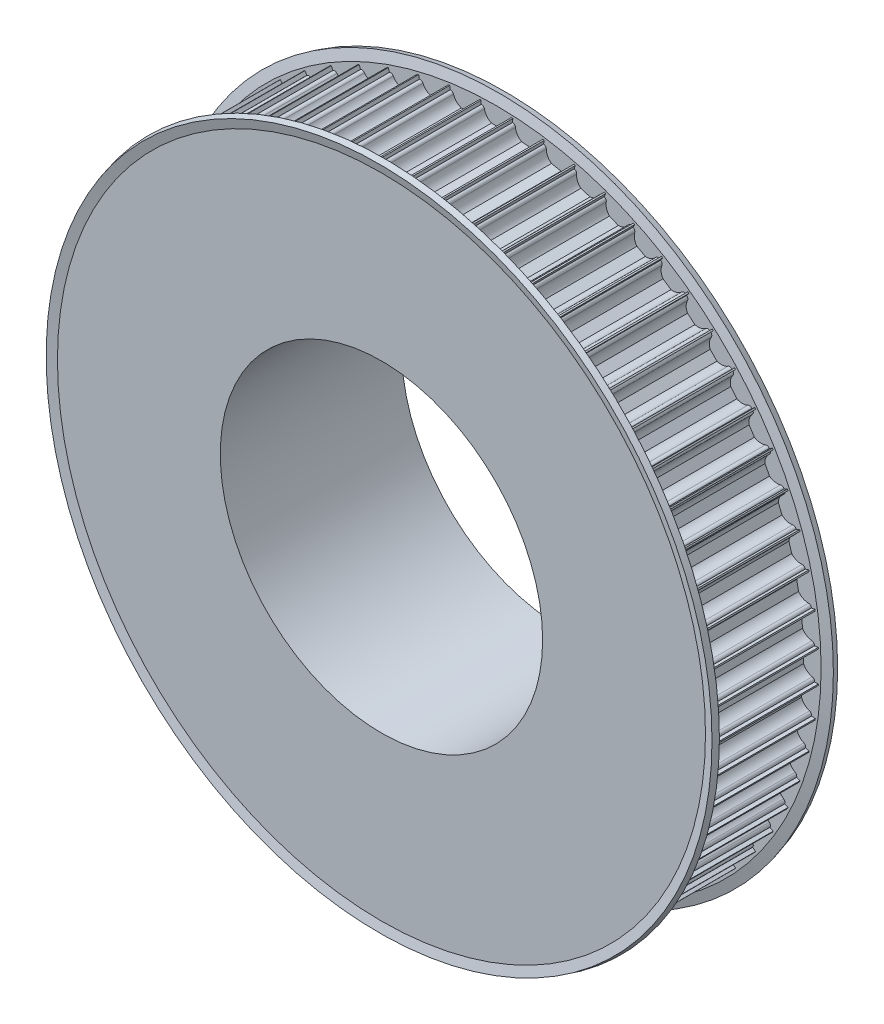
SolidWorks part; units mm, degrees
ref_plane "Front Plane" through (0, 0, 0) normal (0, 0, 1) x (1, 0, 0)
ref_plane "Top Plane" through (0, 0, 0) normal (0, 1, 0) x (1, 0, 0)
ref_plane "Right Plane" through (0, 0, 0) normal (1, 0, 0) x (0, 0, -1)
sketch "Sketch1" plane through (0, 0, 0) normal (1, 0, 0) x (0, 0, -1)
  line L0 (0, 0) -> (39.9222, 0) construction
  line L1 (0, 40) -> (45, 40)
  line L2 (45, 40) -> (45, 55.5)
  line L3 (45, 55.5) -> (30, 55.5)
  line L4 (30, 55.5) -> (30, 80)
  line L5 (30, 80) -> (0, 80)
  line L6 (0, 80) -> (0, 40)
  dimension "D1" = 80
  dimension "D2" = 40
  dimension "D3" = 15.5
  dimension "D4" = 15
  dimension "D5" = 30
revolve "Revolve1" add sketch "Sketch1" angle 360 about L0
sketch "Sketch2" plane through (0, 0, 0) normal (0, 0, 1) x (1, 0, 0)
  line L0 (-3.6742, 79) -> (-3.75, 79)
  line L1 (-3.75, 79) -> (-3.75, 81)
  line L2 (-3.75, 81) -> (3.75, 81)
  line L3 (3.75, 81) -> (3.75, 79)
  line L4 (3.75, 79) -> (3.6742, 79)
  line L5 (1.199, 76.25) -> (-1.199, 76.25)
  arc A0 (-2.9394, 78.4) -> (-1.199, 76.25) centre (0, 79) ccw
  arc A1 (-2.9394, 78.4) -> (-3.6742, 79) centre (-3.6742, 78.25) ccw
  arc A2 (2.9394, 78.4) -> (3.6742, 79) centre (3.6742, 78.25) cw
  arc A3 (1.199, 76.25) -> (2.9394, 78.4) centre (0, 79) ccw
  point P9 (0, 81)
  point P12 (-3, 79)
  point P15 (3, 79)
  dimension "D1" = 3
  dimension "D5" = 0.75
  dimension "D6" = 0.75
  dimension "D2" = 79
  dimension "D3" = 7.5
  dimension "D4" = 2
  dimension "D7" = 2.75
extrude "Cut-Extrude1" cut sketch "Sketch2" against normal up to next
pattern_circular "CirPattern1" count 64 over 360 about axis through (0, 0, 0) along (0, 0, 1) of "Cut-Extrude1"
sketch "Sketch3" plane through (0, 0, 0) normal (1, 0, 0) x (0, 0, -1)
  line L0 (15, -40.9775) -> (15, -19.268) construction
  line L1 (30, -40.9775) -> (0, -40.9775) construction
  line L2 (45, 55.5) -> (30, 55.5) construction
  line L3 (30, -19.268) -> (0, -19.268) construction
  line L4 (30, 55.5) -> (30, 80.4125)
  line L5 (30, -32.718) -> (30, -30.2873) construction
  line L6 (30, -55.5) -> (30, 55.5) construction
  line L7 (30, 80.4125) -> (30.592, 82.6218)
  line L8 (30.592, 82.6218) -> (29.1431, 83.01)
  line L9 (29.1431, 83.01) -> (28.5, 80.61)
  line L10 (28.5, 80.61) -> (28.5, 55.5)
  line L11 (28.5, 55.5) -> (30, 55.5)
  line L12 (1.5, 55.5) -> (0, 55.5)
  line L13 (1.5, 80.61) -> (1.5, 55.5)
  line L14 (0.8569, 83.01) -> (1.5, 80.61)
  line L15 (-0.592, 82.6218) -> (0.8569, 83.01)
  line L16 (0, 80.4125) -> (-0.592, 82.6218)
  line L17 (0, 55.5) -> (0, 80.4125)
  line L18 (0, 0) -> (45, 0) construction
  line L19 (45, -55.5) -> (45, 55.5) construction
  dimension "D1" = 15
  dimension "D2" = 1.5
  dimension "D3" = 25.11
  dimension "D4" = 2.4
revolve "Revolve2" add sketch "Sketch3" angle 360 about L18
